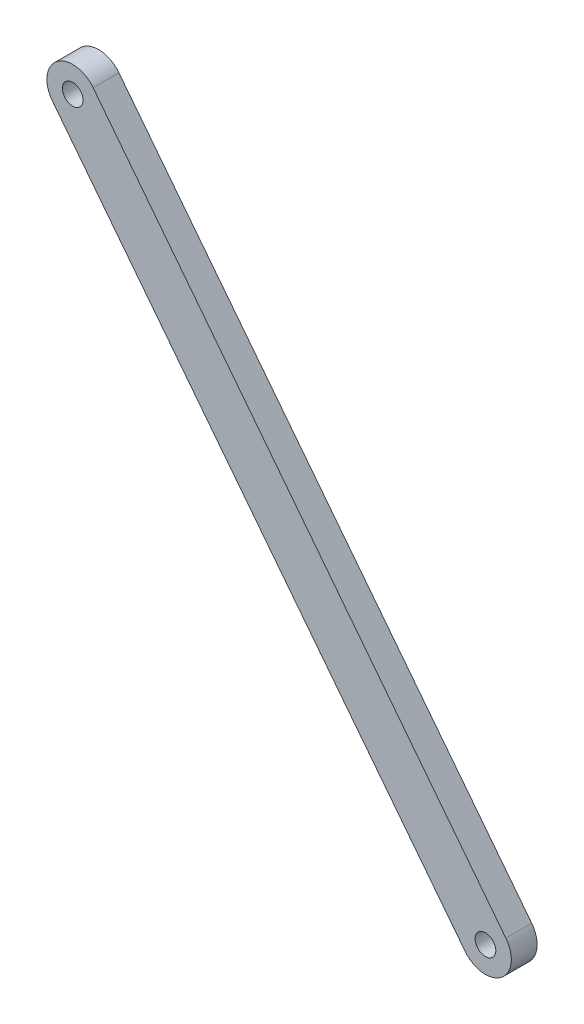
SolidWorks part; units mm, degrees
ref_plane "Front Plane" through (0, 0, 0) normal (0, 0, 1) x (1, 0, 0)
ref_plane "Top Plane" through (0, 0, 0) normal (0, 1, 0) x (1, 0, 0)
ref_plane "Right Plane" through (0, 0, 0) normal (1, 0, 0) x (0, 0, -1)
sketch "Sketch1" plane through (0, 0, 0) normal (0, 0, 1) x (1, 0, 0)
  line L0 (-95.8948, 150.0713) -> (-16.0275, 47.4983)
  line L1 (-23.9177, 41.3546) -> (-103.785, 143.9276)
  circle A0 centre (-19.9726, 44.4264) radius 2 construction
  circle A1 centre (-19.9726, 44.4264) radius 2
  circle A2 centre (-99.8399, 146.9994) radius 2 construction
  circle A3 centre (-99.8399, 146.9994) radius 2
  arc A4 (-16.0275, 47.4983) -> (-23.9177, 41.3546) centre (-19.9726, 44.4264) cw
  arc A5 (-103.785, 143.9276) -> (-95.8948, 150.0713) centre (-99.8399, 146.9994) cw
  dimension "D1" = 5
  dimension "D2" = 5
extrude "Boss-Extrude1" add sketch "Sketch1" along normal blind 5 from offset 5
